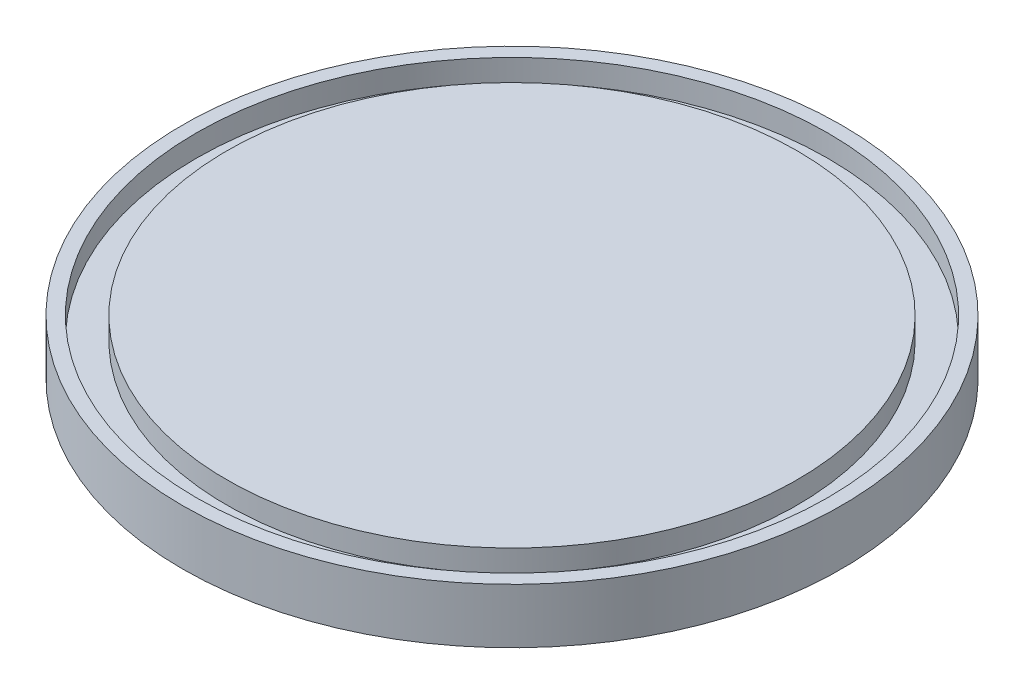
SolidWorks part; units mm, degrees
ref_plane "Front Plane" through (0, 0, 0) normal (0, 0, 1) x (1, 0, 0)
ref_plane "Top Plane" through (0, 0, 0) normal (0, 1, 0) x (1, 0, 0)
ref_plane "Right Plane" through (0, 0, 0) normal (1, 0, 0) x (0, 0, -1)
sketch "Sketch1" plane through (0, 0, 0) normal (0, 0, 1) x (1, 0, 0)
  line L0 (-32.9565, 6.35) -> (-32.9565, 3.81)
  line L1 (0, 0) -> (-38.1, 0)
  line L2 (0, 0) -> (0, 6.35)
  line L3 (0, 6.35) -> (-32.9565, 6.35)
  line L4 (-38.1, 0) -> (-38.1, 6.35)
  line L5 (-32.9565, 3.81) -> (-36.5125, 3.81)
  line L6 (-36.5125, 3.81) -> (-36.5125, 6.35)
  line L7 (-36.5125, 6.35) -> (-38.1, 6.35)
  dimension "D1" = 6.35
  dimension "D2" = 38.1
  dimension "D3" = 2.54
  dimension "D4" = 3.556
  dimension "D5" = 1.5875
revolve "Revolve1" add sketch "Sketch1" angle 360 about L2
